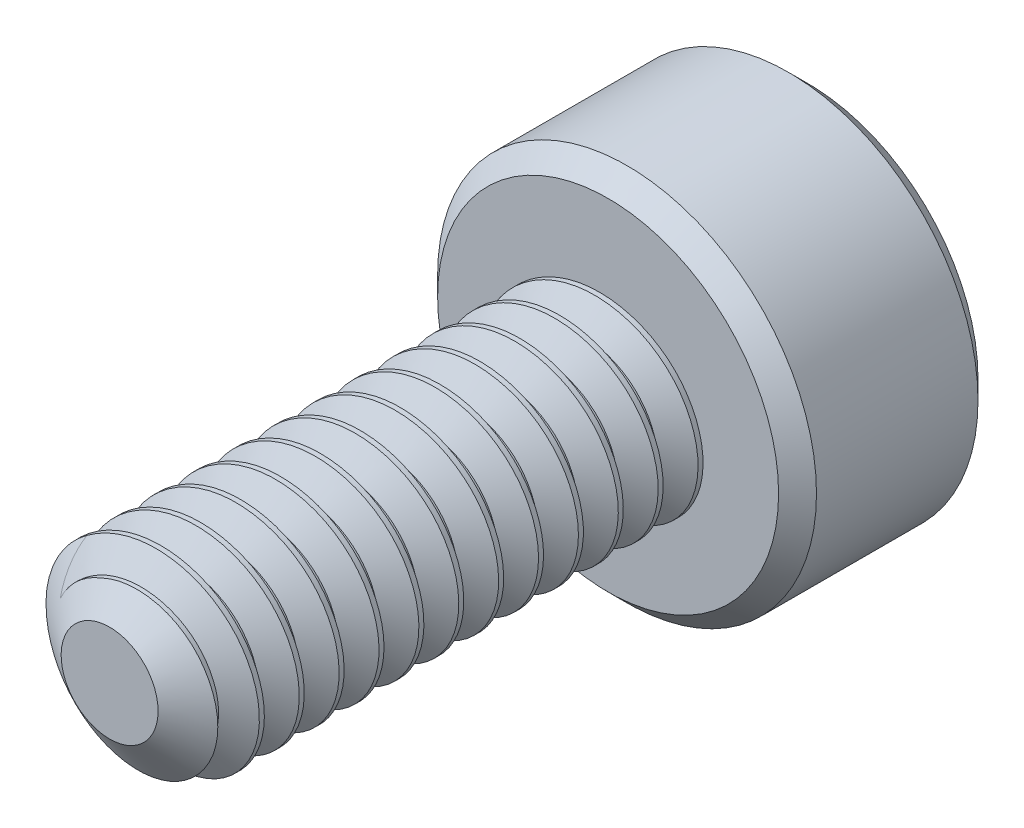
SolidWorks part; units mm, degrees
other "DetailItem1"
material "AISI Type 316L stainless steel"
ref_plane "Front Plane" through (0, 0, 0) normal (0, 0, 1) x (1, 0, 0)
ref_plane "Top Plane" through (0, 0, 0) normal (0, 1, 0) x (1, 0, 0)
ref_plane "Right Plane" through (0, 0, 0) normal (1, 0, 0) x (0, 0, -1)
sketch "Sketch1" plane through (0, 0, 0) normal (0, 0, 1) x (1, 0, 0)
  circle A0 centre (0, 0) radius 1
  dimension "OD" = 2
extrude "Extrude1" add sketch "Sketch1" against normal blind 5
sketch "Sketch2" plane through (0, 0, 0) normal (0, 0, 1) x (1, 0, 0)
  circle A0 centre (0, 0) radius 1 construction
  circle A1 centre (0, 0) radius 1
curve "Helix/Spiral1" pitch 0.4 height 5.4 radius 1 centre (0, 0, 0) axis (0, 0, -1) start towards (0, 1, 0) parameters "pitch"=0.4
sketch "Sketch3" plane through (0, 0, 0) normal (1, 0, 0) x (0, 0, -1)
  line L0 (-0.35, 1) -> (-0.2, 0.7402)
  line L1 (-0.2, 0.7402) -> (-0.15, 0.7402)
  line L2 (-0.15, 0.7402) -> (0, 1)
  line L3 (-0.35, 1) -> (0, 1)
  line L4 (-0.175, 1) -> (-0.175, 0.7402) construction
  line L5 (-0.275, 0.8701) -> (-0.075, 0.8701) construction
  line L6 (0, 1) -> (0, -1) construction
  dimension "D1" = 0.05
  dimension "D2" = 0.2
  dimension "D3" = 60
sweep "Cut-Sweep1" cut profiles "Sketch3" path "Helix/Spiral1" align with end faces yes
sketch "Sketch4" plane through (0, 0, 0) normal (1, 0, 0) x (0, 0, -1)
  line L0 (0.3598, 1) -> (0, 0.4862)
  line L1 (0, 0.4862) -> (0, 1)
  line L2 (0.3598, 1) -> (0, 1)
  line L3 (-0.35, 1) -> (0, 1) construction
  line L4 (0, 0) -> (7.0209, 0) construction
  dimension "D1" = 55
  dimension "D2" = 0.254
revolve "Cut-Revolve1" cut sketch "Sketch4" angle 360 about L4
sketch "Sketch6" plane through (0, 0, -5) normal (0, 0, -1) x (-1, 0, 0)
  circle A0 centre (0, 0) radius 1.9
  dimension "head dia" = 3.8
extrude "Extrude2" add sketch "Sketch6" along normal blind 2
sketch "Sketch7" plane through (0, 0, -7) normal (0, 0, -1) x (-1, 0, 0)
  line L1 (0, 0.866) -> (-0.75, 0.433)
  line L2 (-0.75, 0.433) -> (-0.75, -0.433)
  line L3 (-0.75, -0.433) -> (0, -0.866)
  line L4 (0, -0.866) -> (0.75, -0.433)
  line L5 (0.75, -0.433) -> (0.75, 0.433)
  line L6 (0.75, 0.433) -> (0, 0.866)
  circle A0 centre (0, 0) radius 0.75 construction
  dimension "hex dia" = 1.5
extrude "Cut-Extrude1" cut sketch "Sketch7" against normal blind 1.125
sketch "Sketch8" plane through (0, 0, -7) normal (0, 0, -1) x (-1, 0, 0)
  circle A0 centre (0, 0) radius 0.866
extrude "Cut-Extrude2" cut sketch "Sketch8" against normal through all draft 45
chamfer "Chamfer1" distance 0.19 angle 45 2 edges at (-1.9, 0, -7) (-1.9, 0, -5)
sketch "Sketch10" plane through (0, 0, -5) normal (0, 0, 1) x (1, 0, 0)
  circle A1 centre (0, 0) radius 1
  circle A2 centre (0, 0) radius 1
  dimension "D1" = 0
ref_plane "Plane1" through (0, 0, 0) normal (0, 0, 1) x (1, 0, 0)
extrude "partial thread" [suppressed] add sketch "Sketch10" along normal up to surface (36 mm away) separate body up to plane "Plane1"
chamfer "Chamfer2" [suppressed] distance 0.04 angle 45
combine bodies "Combine1" [suppressed] operation type add bodies to combine 107 108
sketch "Sketch9" plane through (0, 0, 0) normal (1, 0, 0) x (0, 0, -1)
  line L0 (0, 1) -> (0, -1) construction
  line L1 (1, 1) -> (1, -1) construction
  dimension "D1" = 1
equation "\"D3@Helix/Spiral1\" = \"screw length@Extrude1\"+\"pitch@Helix/Spiral1\""
equation "\"D1@Sketch3\" = \"pitch@Helix/Spiral1\"*.125"
equation "\"D2@Sketch3\" = \"pitch@Helix/Spiral1\"*.5"
equation "\"D1@Cut-Extrude1\" = \"hex dia@Sketch7\"*.75"
equation "\"D1@Chamfer1\" = \"head dia@Sketch6\"*.05"
equation "\"D1@Sketch9\" = \"pitch@Helix/Spiral1\"*2.5"
equation "\"D1@Chamfer2\"=\"OD@Sketch1\"*.02"
